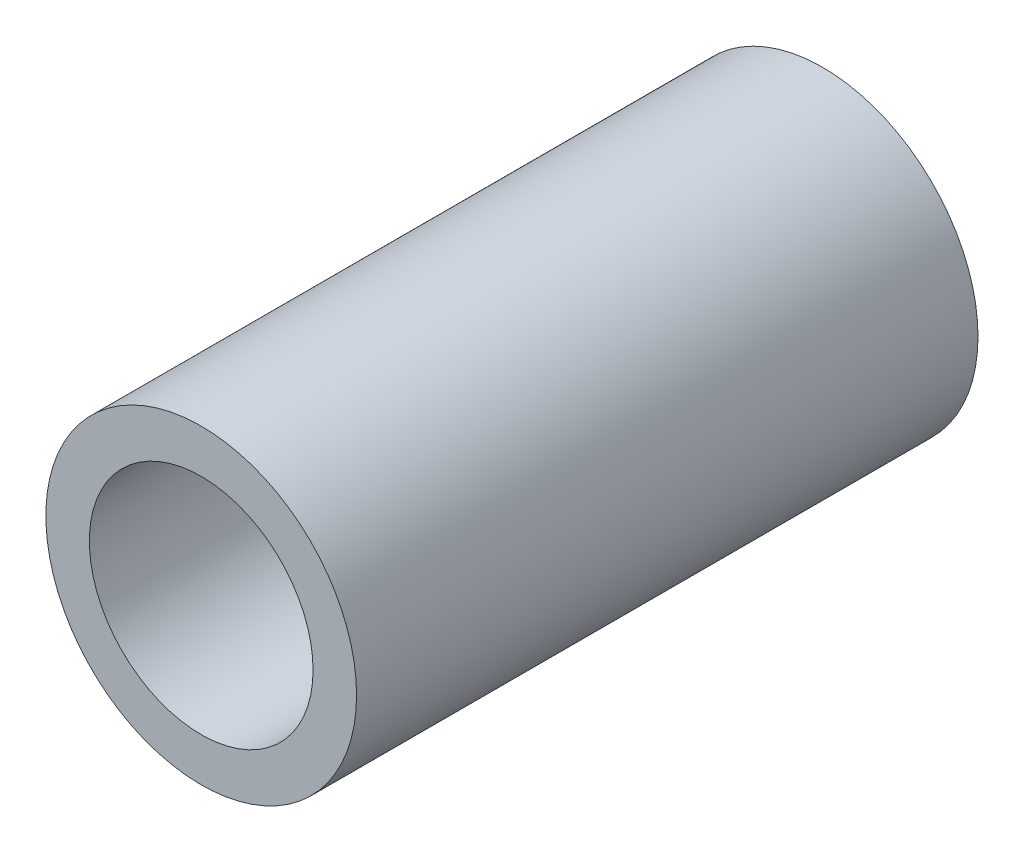
SolidWorks part; units mm, degrees
material "Nylon 6/10"
ref_plane "Front Plane" through (0, 0, 0) normal (0, 0, 1) x (1, 0, 0)
ref_plane "Top Plane" through (0, 0, 0) normal (0, 1, 0) x (1, 0, 0)
ref_plane "Right Plane" through (0, 0, 0) normal (1, 0, 0) x (0, 0, -1)
sketch "Sketch1" plane through (0, 0, 0) normal (0, 0, 1) x (1, 0, 0)
  line L0 (0, 1.143) -> (0, 1.5875) construction
  line L1 (0, -1.143) -> (0, -1.5875) construction
  circle A0 centre (0, 0) radius 1.5875
  circle A1 centre (0, 0) radius 1.143
  dimension "OD" = 3.175
  dimension "ID" = 2.286
sketch "Sketch2" plane through (0, 0, 0) normal (1, 0, 0) x (0, 0, -1)
  line L0 (-3.175, 1.143) -> (3.175, 1.143) construction
  line L1 (-3.175, -1.143) -> (3.175, -1.143) construction
  line L2 (-3.175, -1.5875) -> (3.175, -1.5875) construction
  line L3 (-3.175, 1.5875) -> (3.175, 1.5875) construction
  dimension "Length" = 6.35
extrude "Extrude1" add sketch "Sketch1" along normal up to vertex (3.175 mm away) and the other way up to vertex (3.175 mm away) up to point (0, 1.143, 3.175) other way up to point (0, 1.143, -3.175)
sketch "Sketch3" plane through (0, 0, 3.175) normal (0, 0, 1) x (1, 0, 0)
  circle A0 centre (0, 0) radius 1.143 construction
  circle A3 centre (0, 0) radius 1.143
  point P3 (-1.143, 0)
